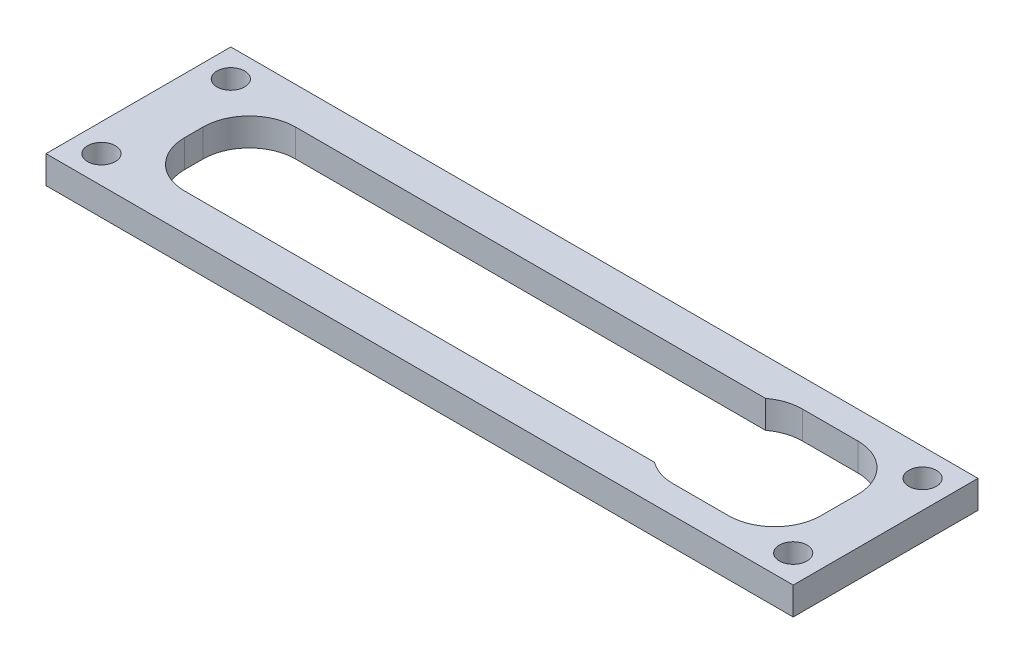
SolidWorks part; units mm, degrees
ref_plane "Front Plane" through (0, 0, 0) normal (0, 0, 1) x (1, 0, 0)
ref_plane "Top Plane" through (0, 0, 0) normal (0, 1, 0) x (1, 0, 0)
ref_plane "Right Plane" through (0, 0, 0) normal (1, 0, 0) x (0, 0, -1)
sketch "Sketch1" plane through (0, 0, 0) normal (0, 1, 0) x (1, 0, 0)
  line L0 (40.4319, 20) -> (40.4319, 0) construction
  line L1 (0, 0) -> (80.8639, 0)
  line L2 (0, 0) -> (0, 20)
  line L3 (0, 20) -> (80.8639, 20)
  line L4 (80.8639, 0) -> (80.8639, 20)
  line L5 (0, 10) -> (80.8639, 10) construction
  line L6 (40.4319, 16) -> (40.4319, 4) construction
  line L7 (6, 16) -> (74.8639, 16)
  line L8 (6, 16) -> (6, 4)
  line L9 (6, 4) -> (74.8639, 4)
  line L10 (74.8639, 16) -> (74.8639, 4)
  line L11 (6, 10) -> (74.8639, 10) construction
  circle A0 centre (3, 17) radius 1.5
  circle A1 centre (3, 3) radius 1.5
  circle A2 centre (77.8639, 3) radius 1.5
  circle A3 centre (77.8639, 17) radius 1.5
  point P17 (40.4319, 10)
  point P18 (40.4319, 10)
  dimension "D7" = 3
  dimension "D1" = 80.8639
  dimension "D2" = 20
  dimension "D3" = 68.8639
  dimension "D4" = 12
  dimension "D5" = 3
  dimension "D6" = 3
extrude "Boss-Extrude1" add sketch "Sketch1" along normal blind 3
sketch "Sketch2" plane through (0, 3, 0) normal (0, 1, 0) x (1, 0, 0)
  line L0 (92, 10) -> (-49908, 10) construction
  line L1 (74.8639, 4) -> (74.8639, 16) construction
  line L2 (61.8639, 17) -> (61.8639, 16)
  line L5 (74.8639, 16) -> (6, 16) construction
  line L6 (68.8639, 17) -> (68.8639, 3) construction
  line L7 (61.8639, 17) -> (75.8639, 17)
  line L9 (61.8639, 3) -> (75.8639, 3)
  line L10 (75.8639, 17) -> (75.8639, 3)
  line L12 (61.8639, 16) -> (74.8639, 16)
  line L13 (74.8639, 16) -> (74.8639, 4)
  line L14 (74.8639, 4) -> (61.8639, 4)
  line L15 (6, 4) -> (74.8639, 4) construction
  line L16 (61.8639, 4) -> (61.8639, 3)
  point P4 (74.8639, 10)
  point P23 (68.8639, 10)
  dimension "D1" = 1
  dimension "D2" = 14
  dimension "D3" = 14
extrude "Cut-Extrude1" cut sketch "Sketch2" against normal through all
fillet "Fillet1" radius 5 6 edges at (75.8639, 1.5, -17) (75.8639, 1.5, -3) (61.8639, 1.5, -17) (61.8639, 1.5, -3) (6, 1.5, -4) (6, 1.5, -16)
equation "\"TrackLength\"= ( ( \"n\" * 28 ) ) / cos ( \"MountAngle\" ) - ( 2 * \"x\" )"
equation "\"D1@Sketch1\"=\"TrackLength\""
equation "\"TrackWidth\"= \"MarbleTrackWidth\" + ( 2 * 4 )"
equation "\"D2@Sketch1\"=\"TrackWidth\""
equation "\"MarbleTrackWidth\"= \"MarbleWidth\" - 1"
equation "\"MarbleTrackLength\"= \"TrackLength\" - ( 2 * 6 )"
equation "\"D3@Sketch1\"=\"MarbleTrackLength\""
equation "\"D4@Sketch1\"=\"MarbleTrackWidth\""
equation "\"MarbleWidth\"= 13"
equation "\"n\"= 3"
equation "\"MountAngle\"= 10"
equation "\"x\"= 14 / cos ( \"MountAngle\" ) - 12"
